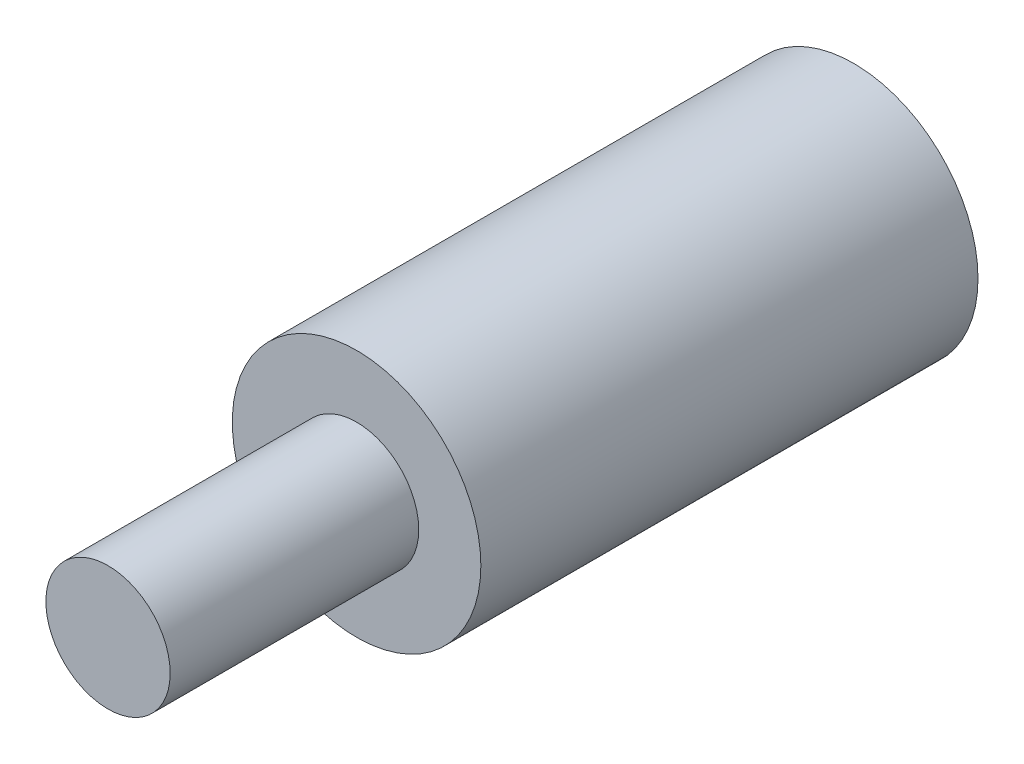
SolidWorks part; units mm, degrees
ref_plane "前视基准面" through (0, 0, 0) normal (0, 0, 1) x (1, 0, 0)
ref_plane "上视基准面" through (0, 0, 0) normal (0, 1, 0) x (1, 0, 0)
ref_plane "右视基准面" through (0, 0, 0) normal (1, 0, 0) x (0, 0, -1)
sketch "草图1" plane through (0, 0, 0) normal (0, 0, 1) x (1, 0, 0)
  circle A0 centre (0, 0) radius 10
  circle A1 centre (0, 0) radius 5
extrude "凸台-拉伸1" add sketch "草图1" along normal blind 20 contours A1 region at (0, 0, 0)
extrude "凸台-拉伸2" add sketch "草图1<3>" against normal blind 40 contours A1 | A0 A1 region at (-9.7172, 0, 0) region at (0, 0, 0)
sketch "草图1<3>" plane through (0, 0, 0) normal (0, 0, 1) x (1, 0, 0) same geometry as "草图1"
